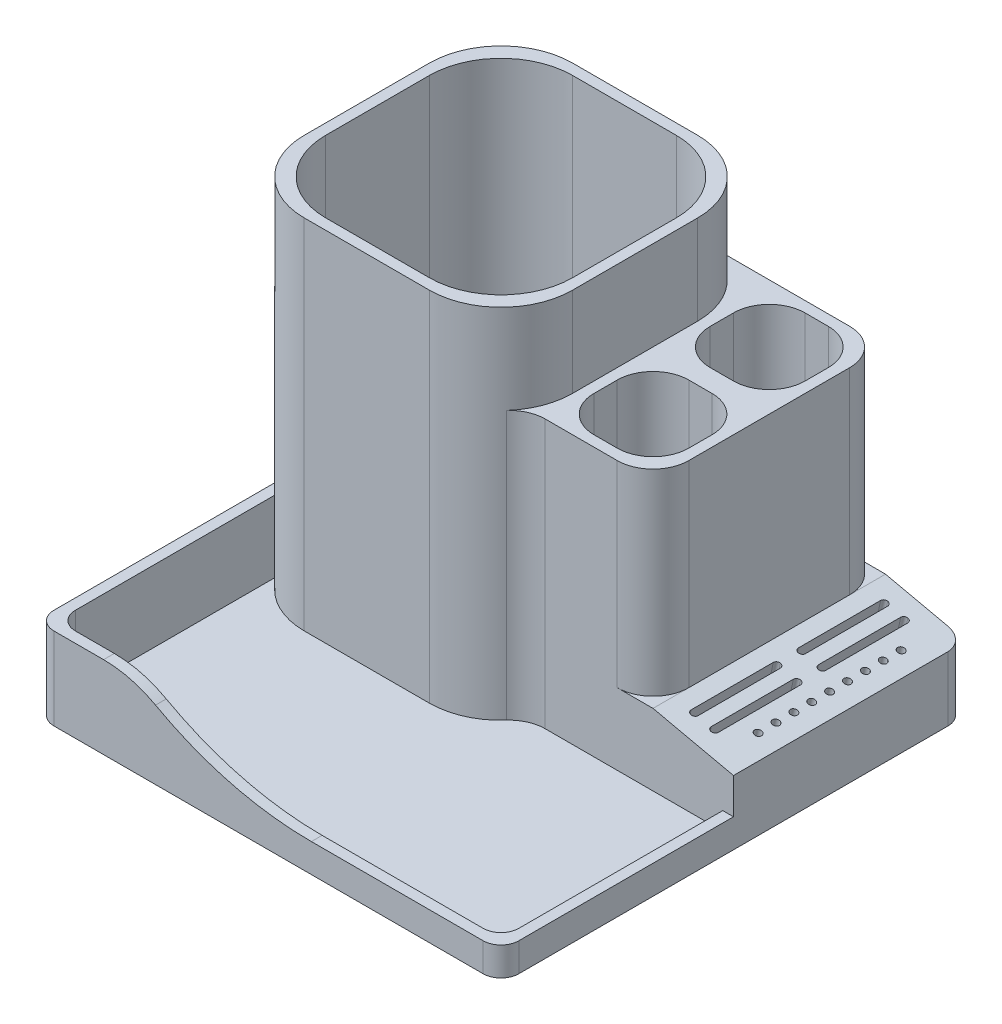
SolidWorks part; units mm, degrees
ref_plane "Спереди" through (0, 0, 0) normal (0, 0, 1) x (1, 0, 0)
ref_plane "Сверху" through (0, 0, 0) normal (0, 1, 0) x (1, 0, 0)
ref_plane "Справа" through (0, 0, 0) normal (1, 0, 0) x (0, 0, -1)
sketch "Эскиз1" plane through (0, 0, 0) normal (0, 1, 0) x (1, 0, 0)
  line L1 (0, 0) -> (-130, 0)
  line L2 (0, 0) -> (0, 130)
  line L3 (0, 130) -> (-130, 130)
  line L4 (-130, 0) -> (-130, 130)
  dimension "D1" = 130
  dimension "D2" = 130
extrude "Бобышка-Вытянуть1" add sketch "Эскиз1" along normal blind 3
sketch "Эскиз2" plane through (0, 3, 0) normal (0, 1, 0) x (1, 0, 0)
  line L0 (-130, 55) -> (-55, 130) construction
  line L1 (-130, 130) -> (-55, 130)
  line L2 (-130, 130) -> (-130, 55)
  line L3 (-130, 55) -> (-55, 55)
  line L4 (-55, 130) -> (-55, 55)
  line L5 (-130, 130) -> (-55, 55) construction
  line L6 (-55, 55) -> (-54.4683, 54.7826) construction
  line L8 (-127, 127) -> (-58, 127)
  line L9 (-127, 127) -> (-127, 58)
  line L10 (-127, 58) -> (-58, 58)
  line L11 (-58, 127) -> (-58, 58)
  line L12 (-127, 127) -> (-58, 58) construction
  line L13 (-127, 58) -> (-58, 127) construction
  point P5 (-92.5, 92.5)
  dimension "D1" = 3
  dimension "D2" = 75
extrude "Бобышка-Вытянуть2" add sketch "Эскиз2" along normal blind 100
sketch "Эскиз3" plane through (0, 3, 0) normal (0, 1, 0) x (1, 0, 0)
  line L0 (-55, 97.5) -> (-22.5, 130) construction
  line L1 (-55, 130) -> (-22.5, 130)
  line L2 (-55, 130) -> (-55, 97.5)
  line L3 (-55, 97.5) -> (-22.5, 97.5)
  line L4 (-22.5, 130) -> (-22.5, 97.5)
  line L5 (-55, 97.5) -> (-22.5, 97.5)
  line L6 (-55, 97.5) -> (-55, 65)
  line L7 (-55, 65) -> (-22.5, 65)
  line L8 (-22.5, 97.5) -> (-22.5, 65)
  line L9 (-22.5, 130) -> (-31.9264, 129.8019) construction
  line L10 (-55, 130) -> (-22.5, 97.5) construction
  line L11 (-55, 65) -> (-22.5, 97.5) construction
  line L12 (-55, 97.5) -> (-22.5, 65) construction
  line L14 (-52, 127) -> (-25.5, 127)
  line L15 (-52, 127) -> (-52, 100.5)
  line L16 (-52, 100.5) -> (-25.5, 100.5)
  line L17 (-25.5, 127) -> (-25.5, 100.5)
  line L18 (-52, 127) -> (-25.5, 100.5) construction
  line L19 (-52, 100.5) -> (-25.5, 127) construction
  line L20 (-52, 94.5) -> (-25.5, 94.5)
  line L21 (-52, 94.5) -> (-52, 68)
  line L22 (-52, 68) -> (-25.5, 68)
  line L23 (-25.5, 94.5) -> (-25.5, 68)
  line L24 (-52, 94.5) -> (-25.5, 68) construction
  line L25 (-52, 68) -> (-25.5, 94.5) construction
  point P7 (-38.75, 113.75)
  point P13 (-38.75, 81.25)
  line M1 (-55, 130) -> (-55, 55)
  line M6 (0, 130) -> (-55, 130)
  dimension "D1" = 32.5
  dimension "D2" = 32.5
  dimension "D3" = 32.5
  dimension "D4" = 3
  dimension "D5" = 3
  dimension "D6" = 3
  dimension "D7" = 3
extrude "Бобышка-Вытянуть3" add sketch "Эскиз3" along normal blind 75 contours L4 L3 L14 L17 L16 L15 M6 M1 | L8 L3 L7 L20 L23 L22 L21 M1 region at (-38.75, 3, -129.5404) region at (-38.75, 3, -97.0404)
fillet "Скругление2" radius 20 2 edges at (-130, 51.5, -130) (-127, 53, -127)
fillet "Скругление3" radius 20 4 edges at (-58, 53, -58) (-55, 53, -55) (-58, 53, -127)
sketch "Эскиз4" plane through (0, 3, 0) normal (0, 1, 0) x (1, 0, 0)
  line L0 (-130, 0) -> (0, 0) construction
  line L1 (-130, 55) -> (-127, 55)
  line L2 (-130, 55) -> (-130, 0)
  line L3 (-130, 0) -> (-127, 0)
  line L4 (-127, 55) -> (-127, 0)
  line L5 (0, 0) -> (0, 130) construction
  line L6 (-127, 0) -> (0, 0)
  line L7 (-127, 0) -> (-127, 3)
  line L8 (-127, 3) -> (0, 3)
  line L9 (0, 0) -> (0, 3)
  line L15 (0, 3) -> (-3, 3)
  line L16 (0, 3) -> (0, 65)
  line L17 (0, 65) -> (-3, 65)
  line L18 (-3, 3) -> (-3, 65)
  line L19 (-22.5, 65) -> (0, 65)
  line M2 (-75, 55) -> (-130, 55)
  line M3 (-130, 55) -> (-130, 0)
  line M4 (-130, 0) -> (0, 0)
  line M5 (0, 0) -> (0, 130)
  dimension "D1" = 3
  dimension "D2" = 3
  dimension "D3" = 3
fillet "Скругление6" radius 10 9 edges at (-57.6795, 40.5, -65) (-25.5, 40.5, -100.5) (-25.5, 40.5, -94.5) (-52, 40.5, -94.5) (-52, 40.5, -100.5) (-52, 40.5, -127) (-52, 40.5, -68) (-25.5, 40.5, -68) (-25.5, 40.5, -127)
extrude "Бобышка-Вытянуть7" add sketch "Эскиз4" along normal blind 20 contours L18 L8 L17 M5 | L8 L4 M4 M5 | L4 M2 M3 M4 region at (-128.5, 3, -27.5) region at (-63.5, 3, -1.5) region at (-1.5, 3, -34)
sketch "Эскиз14" plane through (0, 3, 0) normal (0, 1, 0) x (1, 0, 0)
  line L1 (-22.5, 130) -> (0, 130)
  line L2 (-22.5, 130) -> (-22.5, 65)
  line L3 (-22.5, 65) -> (0, 65)
  line L4 (0, 130) -> (0, 65)
extrude "Бобышка-Вытянуть8" add sketch "Эскиз14" along normal blind 20
sketch "Эскиз15" plane through (0, 0, 0) normal (0, 0, 1) x (1, 0, 0)
  line L0 (-130, 23) -> (0, 23) construction
  line L1 (-102.7518, 23) -> (0, 23)
  line L2 (-102.7518, 23) -> (-102.7518, 8)
  line L3 (-102.7518, 8) -> (0, 8)
  line L4 (0, 23) -> (0, 8)
  line L5 (0, 23) -> (0, 0) construction
  line M2 (0, 0) -> (0, 23)
  line M3 (0, 23) -> (-130, 23)
  dimension "D1" = 8
extrude "Вырез-Вытянуть6" cut sketch "Эскиз15" against normal blind 3 contours L3 M3 M2 region at (-51.3759, 15.5, 0)
fillet "Скругление7" radius 90 1 edges at (-102.7518, 8, -1.5)
fillet "Скругление8" radius 30 1 edges at (-102.7518, 23, -1.5)
sketch "Эскиз17" plane through (0, 0, 0) normal (1, 0, 0) x (0, 0, -1)
  line L1 (3, 8) -> (65, 8)
  line L2 (3, 8) -> (3, 23)
  line L3 (3, 23) -> (65, 23)
  line L4 (65, 8) -> (65, 23)
extrude "Вырез-Вытянуть8" cut sketch "Эскиз17" against normal blind 3
fillet "Скругление9" radius 5 5 edges at (0, 11.5, -130) (-3, 5.5, -3) (0, 4, 0) (-127, 13, -3) (-130, 11.5, 0)
fillet "Скругление11" radius 20 1 edges at (-127, 53, -58)
fillet "Скругление12" radius 20 1 edges
fillet "Скругление13" radius 10 2 edges at (-22.5, 50.5, -65) (-22.5, 50.5, -130)
sketch "Эскиз18" plane through (0, 0, -65) normal (0, 0, 1) x (1, 0, 0)
  line L0 (-22.5, 23) -> (0, 18)
  line L1 (0, 23) -> (-32.5, 23) construction
  line L2 (-22.5, 78) -> (-22.5, 23) construction
  line L3 (0, 8) -> (0, 23) construction
  line L4 (0, 18) -> (0, 23)
  line L5 (0, 23) -> (-22.5, 23)
  dimension "D1" = 5
extrude "Вырез-Вытянуть9" cut sketch "Эскиз18" against normal blind 300
sketch "Эскиз19" plane through (3.8118, 17.1529, 0) normal (0.2169, 0.9762, 0) x (0.9762, -0.2169, 0)
  line L0 (-15.4292, 130) -> (-15.4292, 65) construction
  line L1 (-26.9536, 130) -> (-3.9047, 130)
  line L2 (-26.9536, 130) -> (-26.9536, 65)
  line L3 (-26.9536, 65) -> (-3.9047, 65)
  line L4 (-3.9047, 130) -> (-3.9047, 65)
  line L5 (-16.4292, 100) -> (-16.4292, 125)
  line L6 (-16.4292, 70) -> (-14.4292, 70)
  line L7 (-16.4292, 70) -> (-16.4292, 95)
  line L8 (-16.4292, 95) -> (-14.4292, 95)
  line L9 (-14.4292, 70) -> (-14.4292, 95)
  line L10 (-16.4292, 70) -> (-14.4292, 95) construction
  line L11 (-16.4292, 95) -> (-14.4292, 70) construction
  line L12 (-16.4292, 100) -> (-14.4292, 100)
  line L13 (-14.4292, 100) -> (-14.4292, 125)
  line L14 (-16.4292, 125) -> (-14.4292, 125)
  line L15 (-15.4292, 130) -> (-3.9047, 130) construction
  line L16 (-9.667, 130) -> (-9.667, 65) construction
  line L17 (-26.9536, 97.5) -> (-3.9047, 97.5) construction
  line L18 (-26.9536, 130) -> (-15.4292, 130) construction
  line L19 (-15.4292, 130) -> (-21.1914, 130) construction
  line L20 (-21.1914, 130) -> (-21.1914, 65) construction
  line L21 (-16.4292, 70) -> (-16.1759, 70) construction
  line L22 (-16.4292, 70) -> (-26.9536, 70) construction
  line L23 (-22.1914, 125) -> (-22.1914, 100)
  line L24 (-22.1914, 95) -> (-20.1914, 95)
  line L25 (-22.1914, 95) -> (-22.1914, 70)
  line L26 (-22.1914, 70) -> (-20.1914, 70)
  line L27 (-20.1914, 95) -> (-20.1914, 70)
  line L28 (-22.1914, 95) -> (-20.1914, 70) construction
  line L29 (-22.1914, 70) -> (-20.1914, 95) construction
  line L30 (-22.1914, 125) -> (-20.1914, 125)
  line L31 (-20.1914, 125) -> (-20.1914, 100)
  line L32 (-22.1914, 100) -> (-20.1914, 100)
  circle A0 centre (-9.667, 97.5) radius 1
  circle A1 centre (-9.667, 102.5) radius 1
  circle A2 centre (-9.667, 107.5) radius 1
  circle A3 centre (-9.667, 112.5) radius 1
  circle A4 centre (-9.667, 117.5) radius 1
  circle A5 centre (-9.667, 92.5) radius 1
  circle A6 centre (-9.667, 87.5) radius 1
  circle A7 centre (-9.667, 82.5) radius 1
  circle A8 centre (-9.667, 77.5) radius 1
  point P8 (-15.4292, 82.5)
  point P23 (-21.1914, 82.5)
  dimension "D5" = 5
  dimension "D1" = 25
  dimension "D2" = 2
  dimension "D3" = 5
  dimension "D6" = 2
  dimension "D4" = 2
  dimension "D7" = 2
  dimension "D8" = 5
extrude "Вырез-Вытянуть12" cut sketch "Эскиз19" against normal blind 18 contours A1 | A2 | A3 | A4 | A0 | A5 | A6 | A7 | A8 region at (-5.625, 19.25, -97.5) region at (-5.625, 19.25, -102.5) region at (-5.625, 19.25, -107.5) region at (-5.625, 19.25, -112.5) region at (-5.625, 19.25, -117.5) region at (-5.625, 19.25, -92.5) region at (-5.625, 19.25, -87.5) region at (-5.625, 19.25, -82.5) region at (-5.625, 19.25, -77.5)
extrude "Вырез-Вытянуть13" cut sketch "Эскиз19<4>" against normal blind 20 contours L23 L32 L31 L30 | L27 L24 L25 L26 | L14 L5 L12 L13 | L6 L9 L8 L7 region at (-11.25, 20.5, -112.5) region at (-11.25, 20.5, -82.5) region at (-16.875, 21.75, -112.5) region at (-16.875, 21.75, -82.5)
sketch "Эскиз19<4>" plane through (3.8118, 17.1529, 0) normal (0.2169, 0.9762, 0) x (0.9762, -0.2169, 0) same geometry as "Эскиз19"
fillet "Скругление15" radius 1 16 edges at (-14.3955, 10.9551, -100) (-20.0205, 12.2051, -100) (-14.3955, 10.9551, -125) (-20.0205, 12.2051, -125) (-18.0681, 11.7712, -100) (-12.4431, 10.5212, -100) (-12.4431, 10.5212, -125) (-18.0681, 11.7712, -125) (-12.4431, 10.5212, -95) (-18.0681, 11.7712, -95) (-14.3955, 10.9551, -95) (-20.0205, 12.2051, -95) (-12.4431, 10.5212, -70) (-18.0681, 11.7712, -70) (-14.3955, 10.9551, -70) (-20.0205, 12.2051, -70)
